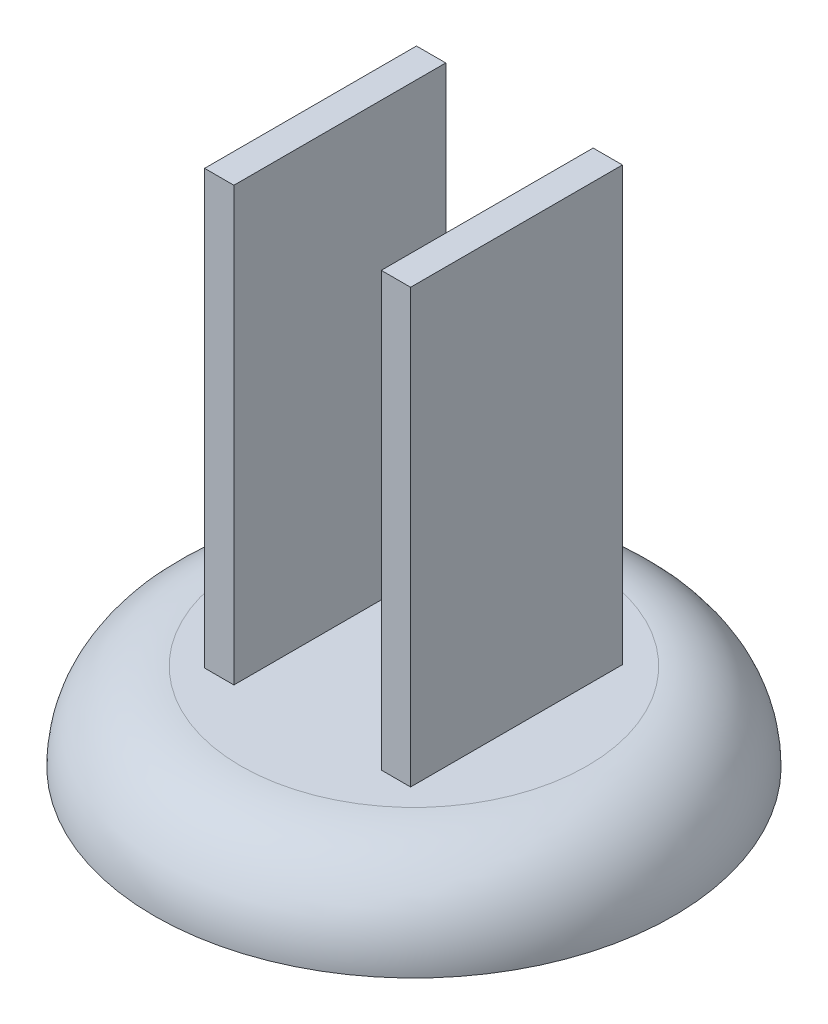
SolidWorks part; units mm, degrees
ref_plane "Front Plane" through (0, 0, 0) normal (0, 0, 1) x (1, 0, 0)
ref_plane "Top Plane" through (0, 0, 0) normal (0, 1, 0) x (1, 0, 0)
ref_plane "Right Plane" through (0, 0, 0) normal (1, 0, 0) x (0, 0, -1)
sketch "Sketch1" plane through (0, 0, 0) normal (0, 1, 0) x (1, 0, 0)
  circle A0 centre (0, 0) radius 3
extrude "Boss-Extrude2" add sketch "Sketch1" along normal blind 1
fillet "Fillet3" radius 1 1 edges at (0, 1, 3)
sketch "Sketch2" [suppressed] plane through (0, 1, 0) normal (0, 1, 0) x (1, 0, 0)
  line L5 (-1, 1) -> (1, -1) construction
  line L6 (-1, -1) -> (1, 1) construction
  circle A0 centre (-1, 1) radius 0.2
  circle A1 centre (1, 1) radius 0.2
  circle A2 centre (1, -1) radius 0.2
  circle A3 centre (-1, -1) radius 0.2
  point P0 (0, 0)
sketch "Sketch3" plane through (0, 0, 0) normal (0, -1, 0) x (-1, 0, 0)
  circle A0 centre (0, 0) radius 2
sketch "Sketch4" plane through (0, 1, 0) normal (0, 1, 0) x (1, 0, 0)
  line L1 (0.8514, 1.219) -> (1.19, 1.219)
  line L2 (0.8514, 1.219) -> (0.8514, -1.2287)
  line L3 (0.8514, -1.2287) -> (1.19, -1.2287)
  line L4 (1.19, 1.219) -> (1.19, -1.2287)
  line L5 (-0.8514, -1.2287) -> (-1.19, -1.2287)
  line L6 (-1.19, 1.219) -> (-1.19, -1.2287)
  line L7 (-0.8514, 1.219) -> (-1.19, 1.219)
  line L8 (-0.8514, 1.219) -> (-0.8514, -1.2287)
extrude "Boss-Extrude3" add sketch "Sketch4" along normal blind 5
